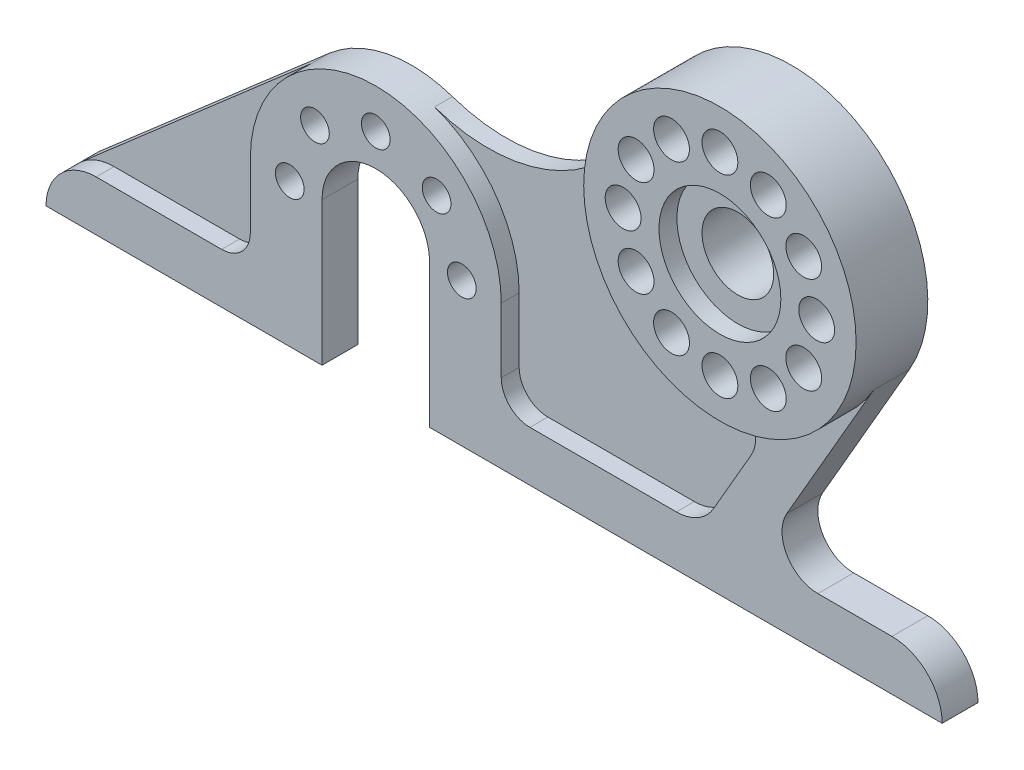
SolidWorks part; units mm, degrees
note: The reader was unsure of these and kept them because the rebuilt part matched: shared geometry of "Эскиз1<3>", "Эскиз1<4>", "Эскиз1<5>".
ref_plane "Спереди" through (0, 0, 0) normal (0, 0, 1) x (1, 0, 0)
ref_plane "Сверху" through (0, 0, 0) normal (0, 1, 0) x (1, 0, 0)
ref_plane "Справа" through (0, 0, 0) normal (1, 0, 0) x (0, 0, -1)
sketch "Эскиз1" plane through (0, 0, 0) normal (0, 0, 1) x (1, 0, 0)
  line L0 (0, 0) -> (0, 126.7558) construction
  line L1 (0, 0) -> (0, -111.1696) construction
  line L2 (-198, -90) -> (-121, -90)
  line L3 (38, -76) -> (17.3205, -76)
  line L4 (0, -76) -> (32.909, -19) construction
  line L5 (-1.3397, -51.9468) -> (-11.7628, -70)
  line L6 (32.909, -19) -> (8.6603, -61)
  line L7 (-22.1551, -76) -> (-63, -76)
  line L8 (-56.796, -50) -> (-288.2419, -50) construction
  line L9 (-71, -50) -> (-71, -68)
  line L10 (-141, -50) -> (-141, -68)
  line L11 (-121, -50) -> (-121, -90)
  line L12 (-91, -50) -> (-91, -90)
  line L13 (-149, -76) -> (-184, -76)
  line L14 (-91, -90) -> (52, -90)
  line L15 (-106, -50) -> (-106, 2.9536) construction
  line L16 (-193.1868, -79.4358) -> (-128.967, -23.5894)
  circle A0 centre (0, 0) radius 10
  circle A1 centre (0, 0) radius 17
  circle A2 centre (0, 0) radius 38
  circle A3 centre (0, 27) radius 5
  circle A4 centre (13.5, 23.3827) radius 5
  circle A5 centre (23.3827, 13.5) radius 5
  circle A6 centre (27, 0) radius 5
  circle A7 centre (23.3827, -13.5) radius 5
  circle A8 centre (13.5, -23.3827) radius 5
  circle A9 centre (0, -27) radius 5
  circle A10 centre (-13.5, -23.3827) radius 5
  circle A11 centre (-23.3827, -13.5) radius 5
  circle A12 centre (-27, 0) radius 5
  circle A13 centre (-23.3827, 13.5) radius 5
  circle A14 centre (-13.5, 23.3827) radius 5
  arc A15 (52, -90) -> (38, -76) centre (38, -90) ccw
  arc A16 (8.6603, -61) -> (17.3205, -76) centre (17.3205, -66) ccw
  arc A17 (-1.3397, -51.9468) -> (-7.9167, -37.1662) centre (-10, -46.9468) ccw
  arc A18 (-22.1551, -76) -> (-11.7628, -70) centre (-22.1551, -64) ccw
  arc A19 (-71, -68) -> (-63, -76) centre (-63, -68) ccw
  arc A20 (-71, -50) -> (-141, -50) centre (-106, -50) ccw
  arc A21 (-149, -76) -> (-141, -68) centre (-149, -68) ccw
  arc A22 (-94.6254, -16.8999) -> (-36.0439, 12.0348) centre (-79.676, 26.6032) ccw
  arc A23 (-121, -50) -> (-91, -50) centre (-106, -50) cw
  circle A24 centre (-106, -26) radius 4
  circle A25 centre (-89.0294, -33.0294) radius 4
  circle A26 centre (-82, -50) radius 4
  circle A27 centre (-89.0294, -66.9706) radius 4 [skipped]
  circle A28 centre (-106, -74) radius 4 [skipped]
  circle A29 centre (-122.9706, -66.9706) radius 4 [skipped]
  circle A30 centre (-130, -50) radius 4
  circle A31 centre (-122.9706, -33.0294) radius 4
  arc A32 (-184, -76) -> (-198, -90) centre (-184, -90) ccw
  point P33 (0, 0)
  point P87 (-106, -50)
  dimension "D1" = 20
  dimension "D2" = 34
  dimension "D3" = 76
  dimension "D4" = 10
  dimension "D10" = 14
  dimension "D11" = 10
  dimension "D12" = 24
  dimension "D13" = 10
  dimension "D14" = 8
  dimension "D16" = 70
  dimension "D17" = 16
  dimension "D18" = 92
  dimension "D19" = 106
  dimension "D20" = 15
  dimension "D21" = 8
  dimension "D25" = 14
  dimension "D5" = 27
  dimension "D7" = 250
  dimension "D8" = 52
  dimension "D9" = 90
  dimension "D15" = 50
  dimension "D22" = 24
  dimension "D6" = 12
  dimension "D23" = 8
extrude "Бобышка-Вытянуть1" add sketch "Эскиз1" along normal blind 10 contours L13 A32 L2 L11 A23 L12 L14 A15 L3 A16 L6 A2 A17 L5 A18 L7 A19 L9 A20 L10 A21 A31 A30 A26 A25 A24
extrude "Бобышка-Вытянуть2" add sketch "Эскиз1<3>" along normal blind 5 contours A32 L13 A21 L10 A20 L16 | A22 A20 L9 A19 L7 A18 L5 A17 A2
sketch "Эскиз1<3>" plane through (0, 0, 0) normal (0, 0, 1) x (1, 0, 0) same geometry as "Эскиз1"
extrude "Бобышка-Вытянуть3" add sketch "Эскиз1<4>" along normal blind 15 separate body contours A1 A0
sketch "Эскиз1<4>" plane through (0, 0, 0) normal (0, 0, 1) x (1, 0, 0) same geometry as "Эскиз1"
extrude "Бобышка-Вытянуть4" add sketch "Эскиз1<5>" along normal blind 20 contours A2 A14 A13 A12 A11 A10 A9 A8 A7 A6 A5 A4 A3 A1
sketch "Эскиз1<5>" plane through (0, 0, 0) normal (0, 0, 1) x (1, 0, 0) same geometry as "Эскиз1"
